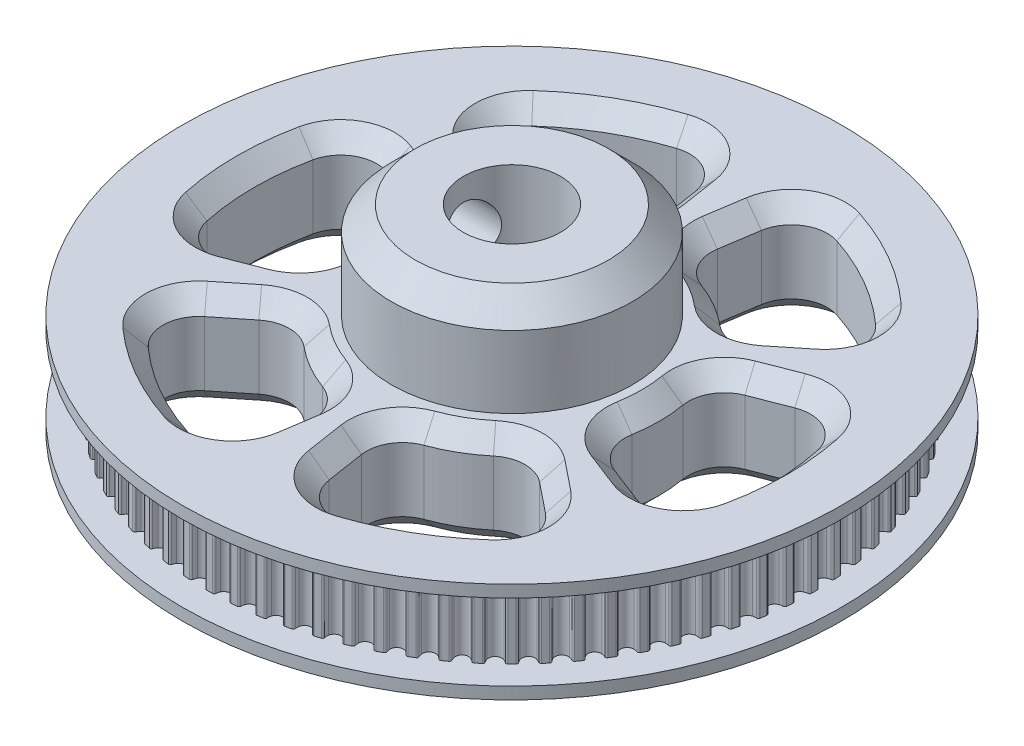
SolidWorks part; units mm, degrees
note: The reader was unsure of these and kept them because the rebuilt part matched: shared geometry of "Sketch3<2>".
ref_plane "Front Plane" through (0, 0, 0) normal (0, 0, 1) x (1, 0, 0)
ref_plane "Top Plane" through (0, 0, 0) normal (0, 1, 0) x (1, 0, 0)
ref_plane "Right Plane" through (0, 0, 0) normal (1, 0, 0) x (0, 0, -1)
sketch "Sketch1" plane through (0, 0, 0) normal (0, 1, 0) x (1, 0, 0)
  circle A0 centre (0, 0) radius 25.4648
  dimension "D1" = 50.9296
extrude "Boss-Extrude1" add sketch "Sketch1" along normal mid plane 6.35
sketch "Sketch2" plane through (0, 0, 0) normal (0, 1, 0) x (1, 0, 0)
  line L0 (0, 0) -> (0, 25.2108) construction
  line L1 (0, 0) -> (0.9821, 24.9965) construction
  line L2 (0, 25.2108) -> (0, 25.4648)
  line L3 (0.9821, 24.9965) -> (0.9997, 25.4452) construction
  line L4 (0.9997, 25.4452) -> (1.3993, 25.4263) construction
  line L5 (1.3993, 25.4263) -> (1.3877, 25.1797) construction
  line L6 (1.978, 25.1331) -> (1.9979, 25.3863)
  arc A1 (0, 25.2108) -> (0.2454, 25.2096) centre (0, 0) cw
  arc A2 (0.2454, 25.2096) -> (0.3931, 25.0753) centre (0.244, 25.0596) cw
  arc A3 (0.3931, 25.0753) -> (0.4763, 24.7681) centre (1.3877, 25.1797) ccw
  arc A4 (0.4763, 24.7681) -> (1.4684, 24.7291) centre (0.9821, 24.9965) ccw
  circle A5 centre (0, 0) radius 25.4648 construction
  arc A6 (0, 25.4648) -> (1.9979, 25.3863) centre (0, 0) cw
  arc A7 (1.5755, 25.0288) -> (1.4684, 24.7291) centre (0.5922, 25.2109) cw
  arc A8 (1.7333, 25.1511) -> (1.5755, 25.0288) centre (1.723, 25.0015) ccw
  arc A9 (1.978, 25.1331) -> (1.7333, 25.1511) centre (0, 0) ccw
  dimension "D2" = 0.15
  dimension "D3" = 1
  dimension "D4" = 0.555
  dimension "D1" = 2.25
  dimension "D5" = 0.254
  dimension "D6" = 0.4
  dimension "D7" = 1.004
extrude "Cut-Extrude1" cut sketch "Sketch2" against normal through all both and the other way through all
pattern_circular "CirPattern1" count 80 over 360 about axis through (0, 0, 0) along (0, 1, 0) of "Cut-Extrude1"
sketch "Sketch3" plane through (0, 0, 0) normal (0, 1, 0) x (1, 0, 0)
  circle A0 centre (0, 0) radius 27.4648
  dimension "D1" = 54.9296
extrude "Boss-Extrude2" add sketch "Sketch3" along normal blind 1 from surface at 3.175 starting at face at (0, 3.175, 0)
extrude "Boss-Extrude3" add sketch "Sketch3<2>" against normal blind 1 from surface at -3.175 starting at face at (0, -3.175, 0)
sketch "Sketch3<2>" plane through (0, 0, 0) normal (0, 1, 0) x (1, 0, 0) same geometry as "Sketch3"
sketch "Sketch4" plane through (0, 0, 0) normal (0, 1, 0) x (1, 0, 0)
  circle A0 centre (0, 0) radius 4.05
  dimension "D1" = 8.1
extrude "Cut-Extrude2" cut sketch "Sketch4" against normal through all both and the other way through all
sketch "Sketch5" plane through (0, 0, 0) normal (0, 1, 0) x (1, 0, 0)
  line L0 (0, 0) -> (0, 21.4648) construction
  line L1 (0, 0) -> (3.2721, 21.2139)
  line L2 (0, 0) -> (-3.2721, 21.2139)
  line L3 (0, 0) -> (16.7358, 13.4407)
  line L4 (0, 0) -> (20.0078, 7.7733)
  line L5 (0, 0) -> (20.0078, -7.7733)
  line L6 (0, 0) -> (16.7358, -13.4407)
  line L7 (0, 0) -> (3.2721, -21.2139)
  line L8 (0, 0) -> (-3.2721, -21.2139)
  line L9 (0, 0) -> (-16.7358, -13.4407)
  line L10 (0, 0) -> (-20.0078, -7.7733)
  line L11 (0, 0) -> (-20.0078, 7.7733)
  line L12 (0, 0) -> (-16.7358, 13.4407)
  circle A1 centre (0, 0) radius 4.05 construction
  circle A4 centre (0, 0) radius 4.05
  circle A6 centre (0, 0) radius 21.4648
  circle A8 centre (0, 0) radius 25.4648
  circle A9 centre (0, 0) radius 25.4648
  circle A10 centre (0, 0) radius 12.3
  circle A11 centre (0, 0) radius 0.55
  point P5 (-1.875, 12.1562)
  point P15 (1.875, 12.1562)
  point P25 (0, 0)
  point P30 (0, 0)
  point P35 (0, 0)
  dimension "D6" = 3.75
  dimension "D1" = 0
  dimension "D2" = 8.25
  dimension "D3" = 3.5
  dimension "D4" = 4
extrude "Cut-Extrude3" cut sketch "Sketch5" against normal through all both and the other way through all contours A10 L2 A6 L12 | A10 L3 A6 L1 | A10 L5 A6 L4 | A10 L11 A6 L10 | A10 L9 A6 L8 | A10 L7 A6 L6
fillet "Fillet2" radius 3 24 edges at (1.875, 0, -12.1562) (3.2721, 0, -21.2139) (-3.2721, 0, -21.2139) (-1.875, 0, -12.1562) (11.4651, 0, -4.4543) (20.0078, 0, -7.7733) (20.0078, 0, 7.7733) (11.4651, 0, 4.4543) (-1.875, 0, 12.1562) (-3.2721, 0, 21.2139) (-16.7358, 0, 13.4407) (-9.5901, 0, 7.7019) (9.5901, 0, 7.7019) (16.7358, 0, 13.4407) (3.2721, 0, 21.2139) (1.875, 0, 12.1562) (-9.5901, 0, -7.7019) (-11.4651, 0, 4.4543) (-20.0078, 0, 7.7733) (-11.4651, 0, -4.4543) (16.7358, 0, -13.4407) (9.5901, 0, -7.7019) (-20.0078, 0, -7.7733) (-16.7358, 0, -13.4407)
chamfer "Chamfer1" distance 1.5 angle 45 96 edges at (6.15, -4.175, -10.6521) (2.6692, -4.175, -12.8442) (10.7324, -4.175, -18.5891) (2.5322, -4.175, -16.4171) (4.1723, -4.175, -20.1056) (-6.15, -4.175, -10.6521) (-2.6692, -4.175, -12.8442) (-2.5322, -4.175, -16.4171) (-10.7324, -4.175, -18.5891) (-4.1723, -4.175, -20.1056) (6.15, 4.175, -10.6521) (10.7324, 4.175, -18.5891) (2.6692, 4.175, -12.8442) (4.1723, 4.175, -20.1056) (2.5322, 4.175, -16.4171) (-6.15, 4.175, -10.6521) (-10.7324, 4.175, -18.5891) (-2.6692, 4.175, -12.8442) (-4.1723, 4.175, -20.1056) (-2.5322, 4.175, -16.4171) (9.7888, -4.175, -8.7337) (12.9515, -4.175, -10.4015) (15.3258, -4.175, -13.6661) (-9.7888, -4.175, -8.7337) (-12.9515, -4.175, -10.4015) (-15.3258, -4.175, -13.6661) (12.9515, 4.175, -10.4015) (9.7888, 4.175, -8.7337) (15.3258, 4.175, -13.6661) (-12.9515, 4.175, -10.4015) (-9.7888, 4.175, -8.7337) (-15.3258, 4.175, -13.6661) (-12.9515, 4.175, 10.4015) (-9.7888, 4.175, 8.7337) (-15.3258, 4.175, 13.6661) (-6.15, 4.175, 10.6521) (-10.7324, 4.175, 18.5891) (-2.6692, 4.175, 12.8442) (-4.1723, 4.175, 20.1056) (-2.5322, 4.175, 16.4171) (-12.9515, -4.175, 10.4015) (-9.7888, -4.175, 8.7337) (-15.3258, -4.175, 13.6661) (-6.15, -4.175, 10.6521) (-10.7324, -4.175, 18.5891) (-2.6692, -4.175, 12.8442) (-4.1723, -4.175, 20.1056) (-2.5322, -4.175, 16.4171) (2.5322, 4.175, 16.4171) (2.6692, 4.175, 12.8442) (4.1723, 4.175, 20.1056) (6.15, 4.175, 10.6521) (10.7324, 4.175, 18.5891) (9.7888, 4.175, 8.7337) (15.3258, 4.175, 13.6661) (12.9515, 4.175, 10.4015) (2.5322, -4.175, 16.4171) (2.6692, -4.175, 12.8442) (4.1723, -4.175, 20.1056) (6.15, -4.175, 10.6521) (10.7324, -4.175, 18.5891) (9.7888, -4.175, 8.7337) (15.3258, -4.175, 13.6661) (12.9515, -4.175, 10.4015) (15.4837, -4.175, 6.0156) (12.458, -4.175, 4.1105) (19.4981, -4.175, 6.4395) (12.3, -4.175, 0) (21.4648, -4.175, 0) (12.458, -4.175, -4.1105) (19.4981, -4.175, -6.4395) (15.4837, -4.175, -6.0156) (15.4837, 4.175, 6.0156) (12.458, 4.175, 4.1105) (19.4981, 4.175, 6.4395) (12.3, 4.175, 0) (21.4648, 4.175, 0) (12.458, 4.175, -4.1105) (19.4981, 4.175, -6.4395) (15.4837, 4.175, -6.0156) (-15.4837, 4.175, 6.0156) (-12.458, 4.175, 4.1105) (-19.4981, 4.175, 6.4395) (-12.3, 4.175, 0) (-21.4648, 4.175, 0) (-12.458, 4.175, -4.1105) (-19.4981, 4.175, -6.4395) (-15.4837, 4.175, -6.0156) (-15.4837, -4.175, 6.0156) (-12.458, -4.175, 4.1105) (-19.4981, -4.175, 6.4395) (-12.3, -4.175, 0) (-21.4648, -4.175, 0) (-12.458, -4.175, -4.1105) (-19.4981, -4.175, -6.4395) (-15.4837, -4.175, -6.0156)
sketch "Sketch6" plane through (0, 4.175, 0) normal (0, 1, 0) x (1, 0, 0)
  circle A0 centre (0, 0) radius 10.05
  circle A1 centre (0, 0) radius 4.05
  circle A2 centre (0, 0) radius 4.05 construction
  dimension "D1" = 6
extrude "Boss-Extrude4" add sketch "Sketch6" along normal blind 8
sketch "Sketch7" plane through (0, 0, 0) normal (1, 0, 0) x (0, 0, -1)
  circle A0 centre (0, 7.8873) radius 2.4036
  dimension "D1" = 4.8072
extrude "Cut-Extrude4" cut sketch "Sketch7" against normal up to next
chamfer "Chamfer2" distance 2 angle 45 1 edges at (0, 12.175, 10.05)
equation "\"n\"= 80"
equation "\"p\"= 2mm"
equation "\"pd\"= ( \"n\" * \"p\" ) / pi"
equation "\"D1@Sketch1\"=\"pd\""
equation "\"D1@Sketch2\"=180/\"n\""
equation "\"D1@CirPattern1\"=\"n\""
equation "\"D1@Sketch3\"=\"pd\"+4mm"
